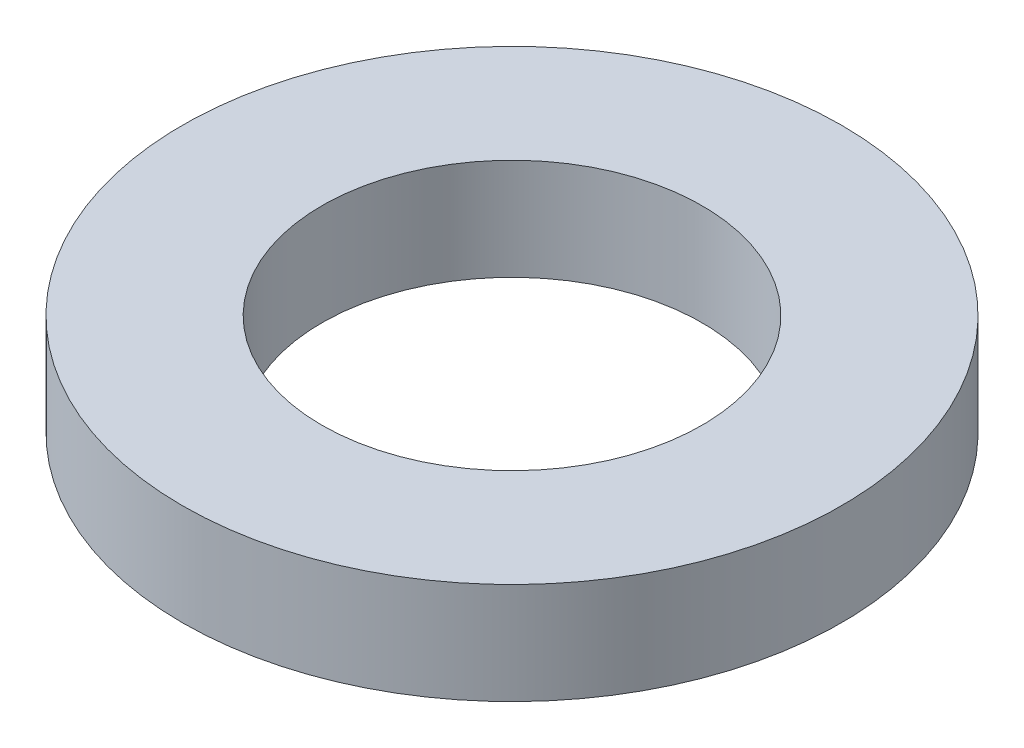
SolidWorks part; units mm, degrees
ref_plane "Front Plane" through (0, 0, 0) normal (0, 0, 1) x (1, 0, 0)
ref_plane "Top Plane" through (0, 0, 0) normal (0, 1, 0) x (1, 0, 0)
ref_plane "Right Plane" through (0, 0, 0) normal (1, 0, 0) x (0, 0, -1)
sketch "Sketch1" plane through (0, 0, 0) normal (0, 1, 0) x (1, 0, 0)
  circle A0 centre (0, 0) radius 65
  dimension "FLANGE_OD" = 130
extrude "Boss-Extrude1" add sketch "Sketch1" along normal blind 20
sketch "Sketch2" plane through (0, 0, 0) normal (0, 1, 0) x (1, 0, 0)
  circle A0 centre (0, 0) radius 37.5
  dimension "BORE_D" = 75
extrude "Cut-Extrude1" cut sketch "Sketch2" along normal through all
sketch "Sketch3" plane through (0, 20, 0) normal (0, 1, 0) x (1, 0, 0)
  circle A0 centre (0, 0) radius 29.2512 construction
  circle A1 centre (-29.2512, 0) radius 4.0463
  dimension "BOLT_D" = 8.0926
  dimension "BOLT_PCD" = 58.5023
extrude "Cut-Extrude2" cut sketch "Sketch3" against normal blind 14.126 rebuild error yes
pattern_circular "CirPattern1" count 6 over 360 rebuild error yes
